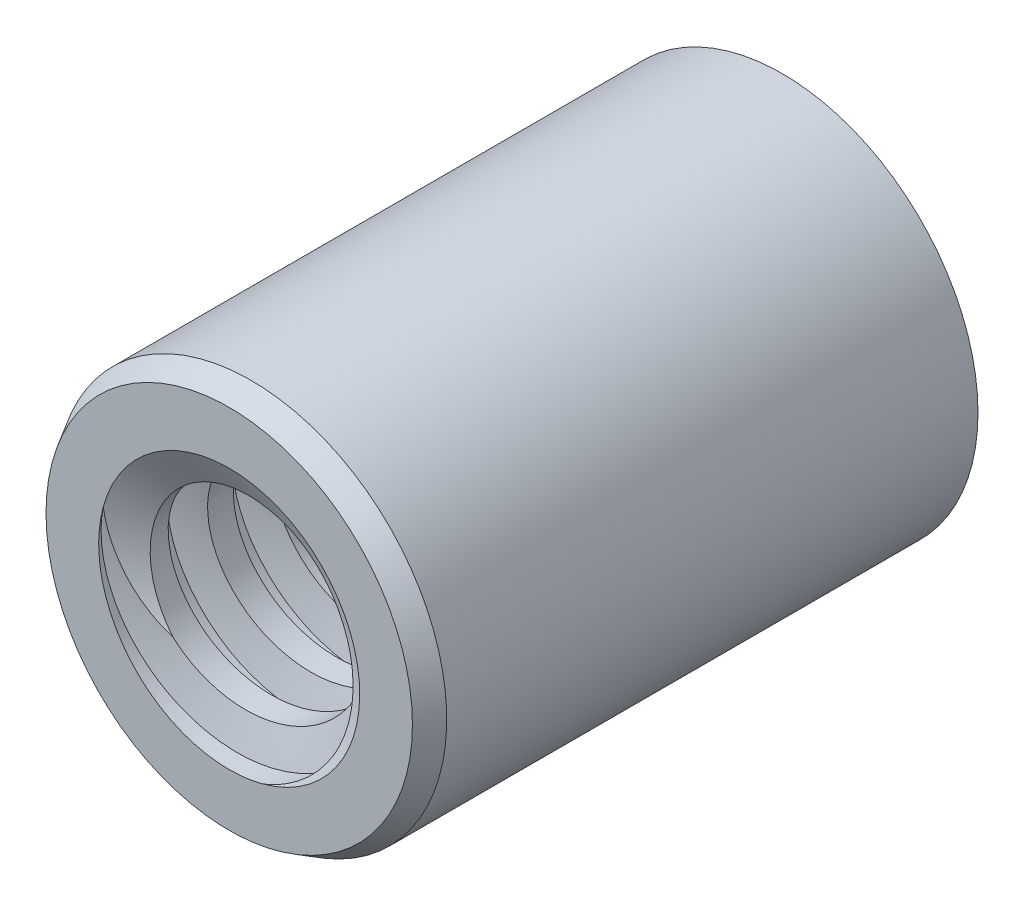
SolidWorks part; units mm, degrees
material "БрАЖ9-4 ГОСТ 18175-78"
ref_plane "Спереди" through (0, 0, 0) normal (0, 0, 1) x (1, 0, 0)
ref_plane "Сверху" through (0, 0, 0) normal (0, 1, 0) x (1, 0, 0)
ref_plane "Справа" through (0, 0, 0) normal (1, 0, 0) x (0, 0, -1)
sketch "Эскиз1" plane through (0, 0, 0) normal (0, 0, 1) x (1, 0, 0)
  circle A0 centre (0, 0) radius 9
  circle A1 centre (0, 0) radius 4.5
  dimension "D1" = 18
  dimension "D2" = 9
extrude "Бобышка-Вытянуть1" add sketch "Эскиз1" along normal blind 26
sketch "Эскиз3" plane through (0, 0, 26) normal (0, 0, 1) x (1, 0, 0)
  circle A0 centre (0, 0) radius 6
  dimension "D1" = 12
curve "Спираль1" pitch 3 height 27.75 turns 9.25
ref_plane "Плоскость1" through (-4.2426, -4.2426, 26) normal (0.7049, -0.7049, -0.0793) x (-0.0561, 0.0561, -0.9968)
chamfer "Фаска1" distance 1.5 angle 30 2 edges at (4.5, 0, 0) (4.5, 0, 26)
sketch "Эскиз4" plane through (-4.2426, -4.2426, 26) normal (0.7049, -0.7049, -0.0793) x (-0.0561, 0.0561, -0.9968)
  line L0 (-0.5, 0) -> (-0.9046, 1.51)
  line L1 (-0.9046, 1.51) -> (0.9046, 1.51)
  line L2 (0.9046, 1.51) -> (0.5, 0)
  line L3 (0.5, 0) -> (-0.5, 0)
  line L5 (0, 0) -> (0, 1.51) construction
  dimension "D1" = 30
  dimension "D2" = 1
  dimension "D3" = 1.51
sweep "Вырез-По траектории2" cut profiles "Эскиз4" path "Спираль1"
chamfer "Фаска2" distance 1 angle 30 2 edges at (9, 0, 0) (9, 0, 26)
